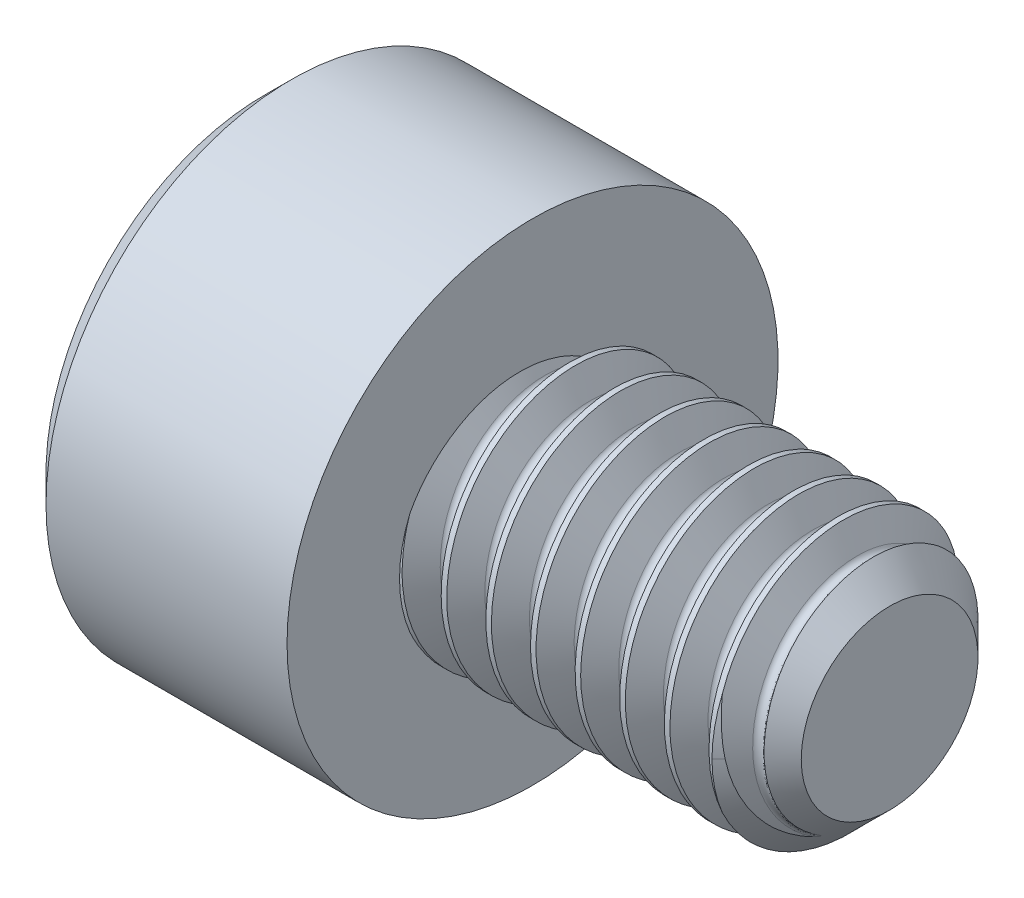
SolidWorks part; units mm, degrees
material "AISI Type 316L stainless steel"
ref_plane "Front Plane" through (0, 0, 0) normal (0, 0, 1) x (1, 0, 0)
ref_plane "Top Plane" through (0, 0, 0) normal (0, 1, 0) x (1, 0, 0)
ref_plane "Right Plane" through (0, 0, 0) normal (1, 0, 0) x (0, 0, -1)
sketch "Sketch1" plane through (0, 0, 0) normal (0, 0, 1) x (1, 0, 0)
  line L0 (-88.7055, 0) -> (96.9812, 0) construction
  line L1 (0, 0) -> (0, 2.75)
  line L2 (0, 2.75) -> (3, 2.75)
  line L4 (7, 0) -> (7, 1.49)
  line L5 (7, 1.49) -> (3, 1.49)
  line L6 (3, 1.49) -> (3, 2.75)
  line L7 (0, 0) -> (7, 0)
revolve "Revolve1" add sketch "Sketch1" angle 360 about L0
chamfer "Chamfer1" distance 0.5 angle 45 1 edges at (7, 0, 1.49)
chamfer "Chamfer2" distance 0.3 angle 45 1 edges at (0, 0, 2.75)
sketch "Sketch3" plane through (0, 0, 0) normal (1, 0, 0) x (0, 0, -1)
  line L1 (-1.4434, 0) -> (-0.7217, -1.25)
  line L2 (-0.7217, -1.25) -> (0.7217, -1.25)
  line L3 (0.7217, -1.25) -> (1.4434, 0)
  line L4 (1.4434, 0) -> (0.7217, 1.25)
  line L5 (0.7217, 1.25) -> (-0.7217, 1.25)
  line L6 (-0.7217, 1.25) -> (-1.4434, 0)
  circle A0 centre (0, 0) radius 1.25 construction
extrude "Cut-Extrude1" cut sketch "Sketch3" along normal blind 2.5
chamfer "Chamfer3" distance 0.3 angle 45 6 edges at (0, 1.25, 0) (0, 0.625, 1.0825) (0, -0.625, 1.0825) (0, -1.25, 0) (0, -0.625, -1.0825) (0, 0.625, -1.0825)
sketch "Sketch5" plane through (7, 0, 0) normal (1, 0, 0) x (0, 0, -1)
  circle A0 centre (0, 0) radius 1.49
curve "Helix/Spiral1" pitch 0.5 height 4 radius 1.49 centre (7, 0, 0) axis (-1, 0, 0) start towards (0, 0, -1)
sketch "Sketch8" plane through (0, 0, 0) normal (0, 1, 0) x (1, 0, 0)
  line L0 (7, 1.49) -> (7, 1.1111) construction
  line L1 (7.0625, 1.2194) -> (7.3281, 1.6794)
  line L2 (7.3281, 1.6794) -> (6.6719, 1.6794)
  line L3 (6.6719, 1.6794) -> (6.9375, 1.2194)
  line L4 (7, -0.99) -> (7, 0.99) construction
  circle A0 centre (7, 1.49) radius 0.1894 construction
  arc A1 (7.0625, 1.2194) -> (6.9375, 1.2194) centre (7, 1.2555) cw
  dimension "D2" = 0.0722
  dimension "D1" = 0.3789
sweep "Cut-Sweep1" cut profiles "Sketch8" path "Helix/Spiral1" align with end faces yes
